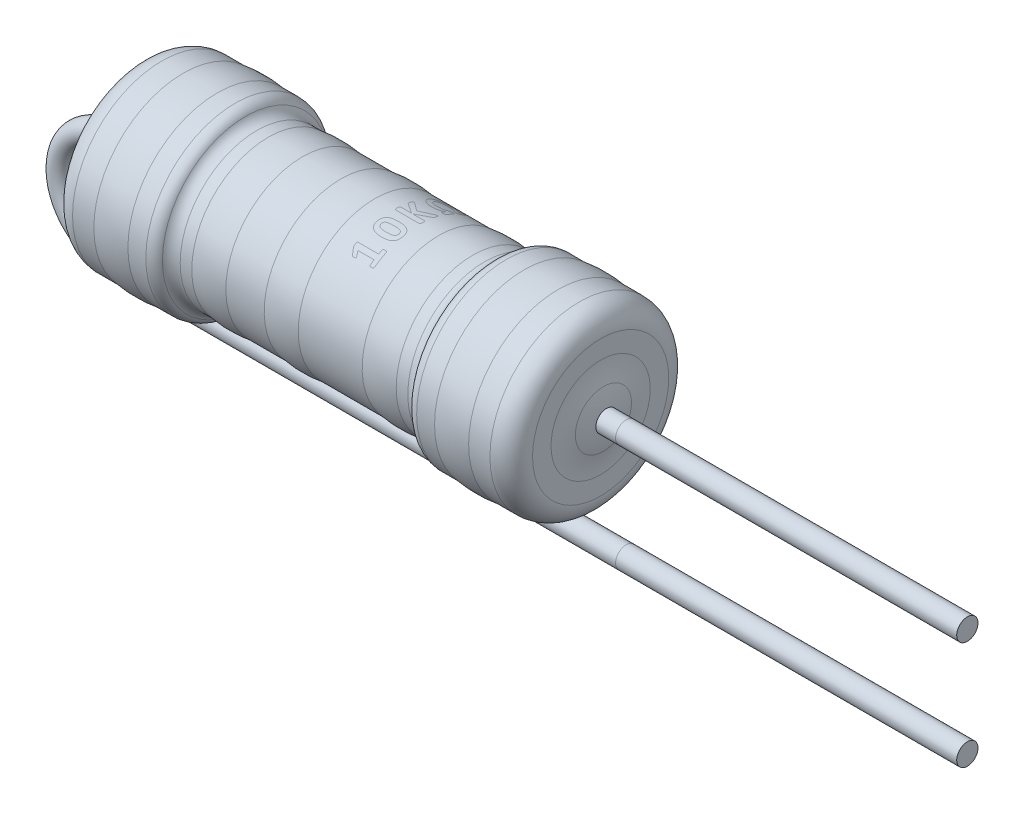
SolidWorks part; units mm, degrees
ref_plane "Front Plane" through (0, 0, 0) normal (0, 0, 1) x (1, 0, 0)
ref_plane "Top Plane" through (0, 0, 0) normal (0, 1, 0) x (1, 0, 0)
ref_plane "Right Plane" through (0, 0, 0) normal (1, 0, 0) x (0, 0, -1)
sketch "Sketch Set Wire Width" plane through (0, 0, 0) normal (0, 0, 1) x (1, 0, 0)
  line L0 (0, 0) -> (6, 0)
  line L1 (6, -2.54) -> (-6, -2.54)
  line L2 (6, 0) -> (14.0102, 0)
  line L3 (-6, 0) -> (-6, -2.54) construction
  line L4 (-6, 0) -> (-6, -2.54) construction
  line L5 (6, -2.54) -> (6, 0) construction
  line L6 (6, -2.54) -> (14.0102, -2.54)
  line L7 (14.0102, -2.54) -> (14.0102, 0) construction
  line L8 (-6, 0) -> (0, 0)
  arc A0 (-6, 0) -> (-6, -2.54) centre (-6, -1.27) ccw
  point P1 (0, 0)
  dimension "D2" = 2.54
  dimension "D3" = 30
  dimension "D1" = 12
  dimension "D4" = 6
sketch "Sketch Wire Diameter" plane through (0, 0, 0) normal (1, 0, 0) x (0, 0, -1)
  circle A0 centre (0, 0) radius 0.25
  dimension "D1" = 0.5
sweep "SET WIRE LENGTH" add profiles "Sketch Wire Diameter" path "Sketch Set Wire Width"
sketch "Sketch3" plane through (0, 0, 0) normal (0, 0, 1) x (1, 0, 0)
  line L0 (-5.4, 0) -> (5.4, 0)
  line L1 (0, 0) -> (0, 1.8) construction
  line L2 (-2.9, 1.8) -> (2.9, 1.8)
  line L3 (-5.4, 0) -> (-5.4, 1.6)
  line L4 (-4.9, 2.1) -> (-3.18, 2.1)
  line L5 (-2.9, 1.82) -> (-2.9, 1.8)
  line L6 (5.4, 0) -> (5.4, 1.6)
  line L7 (4.9, 2.1) -> (3.18, 2.1)
  line L8 (2.9, 1.82) -> (2.9, 1.8)
  arc A0 (-5.4, 1.6) -> (-4.9, 2.1) centre (-4.9, 1.6) cw
  arc A1 (5.4, 1.6) -> (4.9, 2.1) centre (4.9, 1.6) ccw
  arc A2 (-3.18, 2.1) -> (-2.9, 1.82) centre (-3.18, 1.82) cw
  arc A3 (3.18, 2.1) -> (2.9, 1.82) centre (3.18, 1.82) ccw
  dimension "D5" = 0.5
  dimension "D6" = 0.28
  dimension "D1" = 10.8
  dimension "D2" = 5.8
  dimension "D3" = 1.8
  dimension "D4" = 2.1
revolve "Revolve2" add sketch "Sketch3" angle 360 about L0
fillet "Fillet1" radius 0.3 2 edges at (2.9, 0, 1.8) (-2.9, 0, 1.8)
sketch "Sketch5" plane through (0, 0, 0) normal (0, 0, 1) x (1, 0, 0)
  line L0 (0, 0) -> (2, 0) construction
  line L1 (0, 0) -> (-0.3, 0) construction
  line L2 (-0.3, 0) -> (-2, 0) construction
  line L3 (-2, 0) -> (-4, 0) construction
  line L4 (2, 0) -> (4, 0) construction
  line L5 (-4, 0) -> (-4, 2.1) construction
  line L6 (-0.3, 0) -> (-0.3, 1.8) construction
  line L7 (-2, 0) -> (-2, 1.8) construction
  line L8 (2, 0) -> (2, 1.8) construction
  line L9 (4, 0) -> (4, 2.1) construction
  line L10 (-4, 2.1) -> (-4, 2.13) construction
  line L11 (-4.9, 2.1) -> (-3.18, 2.1) construction
  line L12 (4.9, 2.1) -> (3.18, 2.1) construction
  line L13 (-2.9, 1.8) -> (2.9, 1.8) construction
  line L14 (-2, 1.8) -> (-2, 1.83) construction
  line L17 (-4.4, 2.1) -> (-3.6, 2.1)
  line L19 (-5.4, 0) -> (5.4, 0) construction
  line L22 (-2.4, 1.8) -> (-1.6, 1.8) construction
  line L26 (-0.7, 1.8) -> (0.1, 1.8) construction
  line L30 (1.6, 1.8) -> (2.4, 1.8) construction
  line L34 (3.6, 2.1) -> (4.4, 2.1) construction
  line L36 (-0.3, 1.8) -> (-0.3, 1.83) construction
  line L37 (2, 1.8) -> (2, 1.83) construction
  line L38 (4, 2.1) -> (4, 2.13) construction
  arc A0 (-4.4, 2.1) -> (-3.6, 2.1) centre (-4, -0.5517) cw
  arc A1 (-2.4, 1.8) -> (-1.6, 1.8) centre (-2, -0.8517) cw construction
  arc A2 (-0.7, 1.8) -> (0.1, 1.8) centre (-0.3, -0.8517) cw construction
  arc A3 (1.6, 1.8) -> (2.4, 1.8) centre (2, -0.8517) cw construction
  arc A4 (3.6, 2.1) -> (4.4, 2.1) centre (4, -0.5517) cw construction
  dimension "D3" = 0.8
  dimension "D1" = 4
  dimension "D2" = 4
  dimension "D4" = 0.03
  dimension "D5" = 2
  dimension "D6" = 2
  dimension "D7" = 1.7
revolve "Band 1" add sketch "Sketch5" angle 360 about L2
sketch "Sketch8" plane through (0, 0, 0) normal (0, 0, 1) x (1, 0, 0)
  line L0 (-2.4, 1.8) -> (-1.6, 1.8) construction
  line L1 (-2.4, 1.8) -> (-1.6, 1.8)
  arc A0 (-1.6, 1.8) -> (-2.4, 1.8) centre (-2, -0.8517) ccw construction
  arc A1 (-1.6, 1.8) -> (-2.4, 1.8) centre (-2, -0.8517) ccw
revolve "Band 2" add sketch "Sketch8" angle 360 about L2
sketch "Sketch9" plane through (0, 0, 0) normal (0, 0, 1) x (1, 0, 0)
  line L0 (-0.7, 1.8) -> (0.1, 1.8) construction
  line L1 (-0.7, 1.8) -> (0.1, 1.8)
  arc A0 (0.1, 1.8) -> (-0.7, 1.8) centre (-0.3, -0.8517) ccw construction
  arc A1 (0.1, 1.8) -> (-0.7, 1.8) centre (-0.3, -0.8517) ccw
revolve "Band 3" add sketch "Sketch9" angle 360 about L2
sketch "Sketch10" plane through (0, 0, 0) normal (0, 0, 1) x (1, 0, 0)
  line L0 (1.6, 1.8) -> (2.4, 1.8) construction
  line L1 (1.6, 1.8) -> (2.4, 1.8)
  arc A0 (2.4, 1.8) -> (1.6, 1.8) centre (2, -0.8517) ccw construction
  arc A1 (2.4, 1.8) -> (1.6, 1.8) centre (2, -0.8517) ccw
revolve "Band 4" add sketch "Sketch10" angle 360 about L0
sketch "Sketch11" plane through (0, 0, 0) normal (0, 0, 1) x (1, 0, 0)
  line L0 (3.6, 2.1) -> (4.4, 2.1) construction
  line L1 (3.6, 2.1) -> (4.4, 2.1)
  arc A0 (4.4, 2.1) -> (3.6, 2.1) centre (4, -0.5517) ccw construction
  arc A1 (4.4, 2.1) -> (3.6, 2.1) centre (4, -0.5517) ccw
revolve "Band 5" add sketch "Sketch11" angle 360 about L4
sketch "Sketch12" plane through (0, 0, 0) normal (0, 0, 1) x (1, 0, 0)
  line L0 (-5.35, 0) -> (5.35, 0) construction
  line L1 (-5.35, 1) -> (-5.35, 0)
  line L2 (5.35, 1) -> (5.35, 0)
  line L3 (-5.35, 0) -> (-5.55, 0)
  line L4 (5.35, 0) -> (5.55, 0)
  arc A0 (-5.35, 1) -> (-5.55, 0) centre (-2.95, 0) ccw
  arc A1 (5.35, 1) -> (5.55, 0) centre (2.95, 0) cw
  dimension "D3" = 0.2
  dimension "D4" = 2.6
  dimension "D1" = 10.7
  dimension "D2" = 1
revolve "Revolve10" add sketch "Sketch12" angle 360 about L0
fillet "Fillet2" radius 2 2 edges at (5.4, 0, 0.8703) (-5.4, 0, -0.8703)
ref_plane "Plane2" through (0, 3, 0) normal (0, 1, 0) x (1, 0, 0)
sketch "Sketch13" plane through (0, 3, 0) normal (0, 1, 0) x (1, 0, 0)
  line L0 (0, 0) -> (1.15, 0) construction
  line L1 (1.15, 1.75) -> (1.15, -1.75) construction
  text T0 "10KΩ" font "Calibri" height 0.6
  dimension "D1" = 3.5
  dimension "D2" = 1.15
wrap "Wrap1" sketch "Sketch13" wrap type scribe source sketch "Sketch13" face at (0.1, 1.8, 0)
